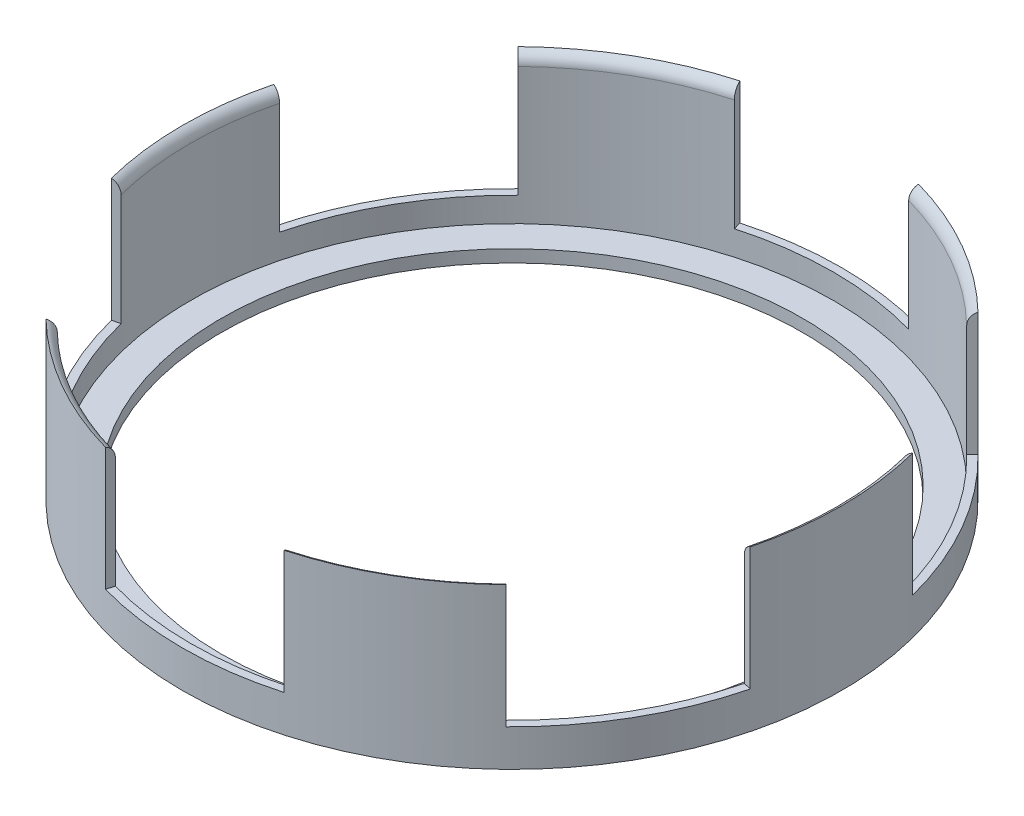
SolidWorks part; units mm, degrees
ref_plane "Front (XY)" through (0, 0, 0) normal (0, 0, 1) x (1, 0, 0)
ref_plane "Top (XZ)" through (0, 0, 0) normal (0, 1, 0) x (1, 0, 0)
ref_plane "Right (YZ)" through (0, 0, 0) normal (1, 0, 0) x (0, 0, -1)
sketch "Sketch1" plane through (0, 0, 0) normal (0, 1, 0) x (1, 0, 0)
  circle A0 centre (0, 0) radius 26.125
  dimension "D1" = 52.25
extrude "Boss-Extrude1" add sketch "Sketch1" along normal blind 1
sketch "Sketch2" plane through (0, 0, 0) normal (0, 0, 1) x (1, 0, 0)
  line L0 (26.125, 0) -> (26.775, 0)
  line L1 (26.775, 0) -> (26.775, 3)
  line L2 (26.775, 3) -> (26.125, 3)
  line L3 (26.125, 3) -> (26.125, 0)
  line L4 (0, 0) -> (0, 3) construction
  dimension "D1" = 0.65
  dimension "D2" = 3
revolve "Revolve1" add sketch "Sketch2" angle 360 about L4
sketch "Sketch3" plane through (0, 0, 0) normal (0, 1, 0) x (1, 0, 0)
  circle A0 centre (0, 0) radius 23.625
  dimension "D1" = 47.25
extrude "Cut-Extrude2" cut sketch "Sketch3" against normal through all and the other way through all
sketch "Sketch5" plane through (0, 0, 0) normal (0, 1, 0) x (1, 0, 0)
  line L0 (0, 0) -> (26.775, 0) construction
  line L1 (25.9488, 6.6) -> (25.3189, 6.4398)
  line L2 (25.9488, -6.6) -> (25.3189, -6.4398)
  circle A0 centre (0, 0) radius 26.775 construction
  arc A1 (25.9488, 6.6) -> (25.9488, -6.6) centre (0, 0) cw
  circle A2 centre (0, 0) radius 26.125 construction
  arc A3 (25.3189, -6.4398) -> (25.3189, 6.4398) centre (0, 0) ccw
  point P9 (26.775, 0)
  dimension "D1" = 13.2
extrude "Boss-Extrude2" add sketch "Sketch5" along normal blind 13
sketch "Sketch6" plane through (0, 0, 0) normal (0, 0, 1) x (1, 0, 0)
  line L0 (0, 0) -> (0, 15.8109) construction
fillet "Fillet1" radius 1 1 edges at (26.125, 13, 0)
pattern_circular "CirPattern1" count 6 over 360 about axis through (0, 0, 0) along (0, 1, 0) of "Boss-Extrude2", "Fillet1" reverse direction yes
